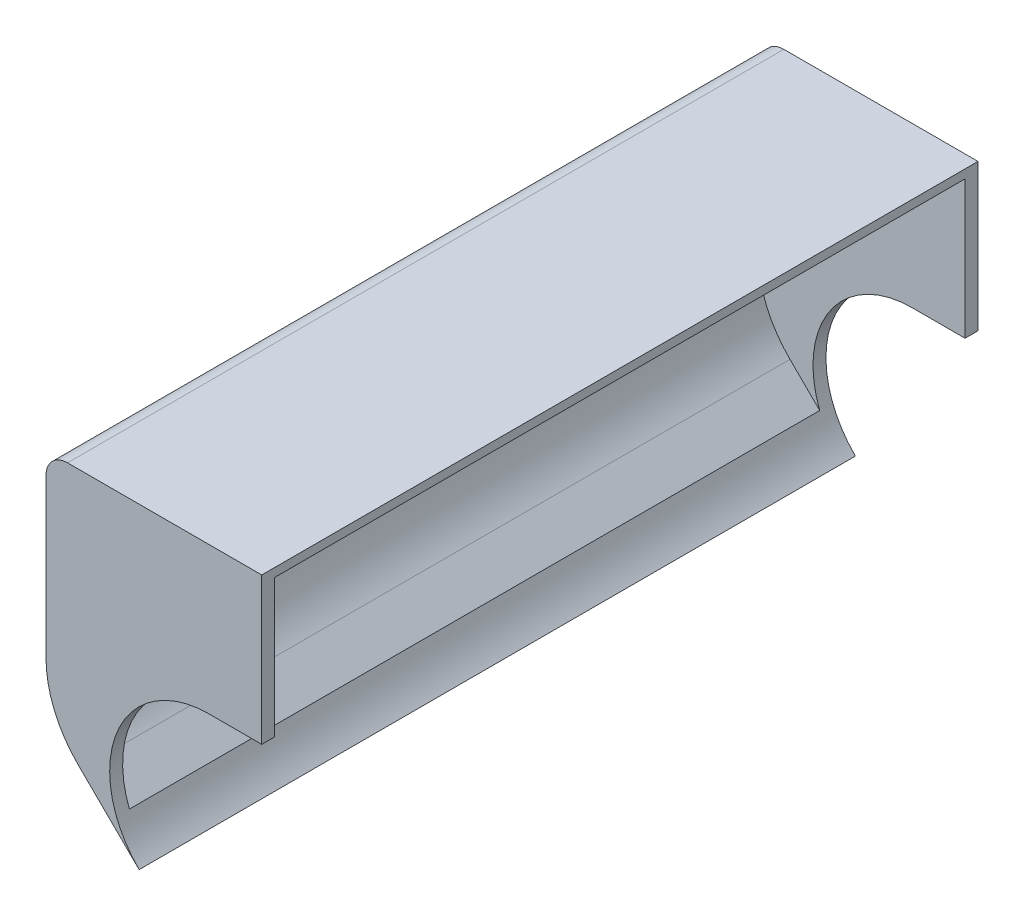
SolidWorks part; units mm, degrees
ref_plane "Front Plane" through (0, 0, 0) normal (0, 0, 1) x (1, 0, 0)
ref_plane "Top Plane" through (0, 0, 0) normal (0, 1, 0) x (1, 0, 0)
ref_plane "Right Plane" through (0, 0, 0) normal (1, 0, 0) x (0, 0, -1)
sketch "Sketch1" plane through (0, 0, 0) normal (0, 0, 1) x (1, 0, 0)
  line L0 (-176.4226, 3.6462) -> (-198.0073, 24.9918)
  line L1 (-198.0073, 24.9918) -> (-198.0073, 77)
  line L2 (-198.0073, 77) -> (-148.0073, 77)
  line L4 (-160.25, 43) -> (-148.0073, 43)
  line L6 (-148.0073, 43) -> (-148.0073, 77)
  arc A1 (-160.25, 43) -> (-176.4226, 3.6462) centre (-160.25, 20) ccw
extrude "Boss-Extrude1" add sketch "Sketch1" against normal blind 3
sketch "Sketch2" plane through (0, 0, -166) normal (0, 0, -1) x (-1, 0, 0)
  line L5 (198.0073, 24.9918) -> (198.0073, 77)
  line L6 (198.0073, 77) -> (148.0073, 77)
  line L7 (148.0073, 77) -> (148.0073, 43)
  line L8 (148.0073, 43) -> (160.25, 43)
  line L9 (176.4226, 3.6462) -> (198.0073, 24.9918)
  line L10 (198.0073, 24.9918) -> (198.0073, 77)
  line L11 (198.0073, 77) -> (148.0073, 77)
  line L12 (148.0073, 77) -> (148.0073, 43)
  line L13 (148.0073, 43) -> (160.25, 43)
  line L14 (176.4226, 3.6462) -> (198.0073, 24.9918)
  arc A1 (176.4226, 3.6462) -> (160.25, 43) centre (160.25, 20) ccw
  arc A2 (176.4226, 3.6462) -> (160.25, 43) centre (160.25, 20) ccw
  dimension "D1" = 0
extrude "Boss-Extrude2" add sketch "Sketch2" against normal blind 3 separate body
sketch "Sketch3" plane through (0, 0, -3) normal (0, 0, -1) x (-1, 0, 0)
  line L0 (181.6864, 11.6645) -> (196.0073, 25.8268)
  line L1 (196.0073, 25.8268) -> (196.0073, 75)
  line L2 (196.0073, 75) -> (148.0073, 75)
  line L3 (148.0073, 77) -> (148.0073, 75)
  line L4 (175.0163, 5.0683) -> (196.0073, 25.8268) construction
  line L5 (198.0073, 24.9918) -> (198.0073, 77)
  line L6 (198.0073, 77) -> (148.0073, 77)
  line L7 (148.0073, 77) -> (148.0073, 43)
  line L8 (148.0073, 43) -> (160.25, 43)
  line L9 (176.4226, 3.6462) -> (198.0073, 24.9918)
  line L10 (198.0073, 24.9918) -> (198.0073, 77)
  line L11 (198.0073, 77) -> (148.0073, 77)
  line L14 (176.4226, 3.6462) -> (198.0073, 24.9918)
  arc A0 (160.25, -3) -> (160.25, 43) centre (160.25, 20) ccw construction
  arc A1 (176.4226, 3.6462) -> (160.25, 43) centre (160.25, 20) ccw
  arc A3 (176.4226, 3.6462) -> (181.6864, 11.6645) centre (160.25, 20) ccw
  dimension "D1" = 0
  dimension "D2" = 2
extrude "Boss-Extrude3" add sketch "Sketch3" along normal up to surface (160 mm away) up to face at (-173.6482, 45.6762, -163)
fillet "Fillet1" radius 5 2 edges at (-198.0073, 77, -83) (-196.0073, 75, -83)
fillet "Fillet2" radius 25 2 edges at (-196.0073, 25.8268, -83) (-198.0073, 24.9918, -83)
sketch "Sketch4" plane through (-198.0073, 0, 0) normal (-1, 0, 0) x (0, 0, 1)
  line L0 (-166, 57) -> (0, 57) construction
  line L3 (-95, 57) -> (-71, 57) construction
  line L4 (-83, 57) -> (-83, 76.9624) construction
  circle A0 centre (-30, 47) radius 2.5
  circle A1 centre (-136, 47) radius 2.5
  circle A2 centre (-95, 57) radius 8.5
  circle A3 centre (-71, 57) radius 8.5
extrude "Cut-Extrude1" cut sketch "Sketch4" against normal blind 7
sketch "Sketch5" plane through (-196.0073, 0, 0) normal (1, 0, 0) x (0, 0, -1)
  line L4 (105.5, 67) -> (60.5, 67)
  line L5 (60.5, 67) -> (60.5, 47)
  line L6 (60.5, 47) -> (105.5, 47)
  line L7 (105.5, 47) -> (105.5, 67)
  line L8 (105.5, 67) -> (60.5, 67)
  line L9 (60.5, 67) -> (60.5, 47)
  line L10 (60.5, 47) -> (105.5, 47)
  line L11 (105.5, 47) -> (105.5, 67)
  circle A0 centre (71, 57) radius 8.5 construction
  circle A1 centre (71, 57) radius 8.5
  circle A2 centre (95, 57) radius 8.5 construction
  circle A3 centre (95, 57) radius 8.5
  dimension "D1" = 0
extrude "Boss-Extrude4" add sketch "Sketch5" along normal blind 8
sketch "Sketch6" plane through (-196.0073, 0, 0) normal (1, 0, 0) x (0, 0, -1)
  circle A0 centre (20.5, 60.4) radius 6
extrude "Cut-Extrude2" cut sketch "Sketch6" against normal up to surface (2 mm away) up to face at (-198.0073, 47, -27.5)
